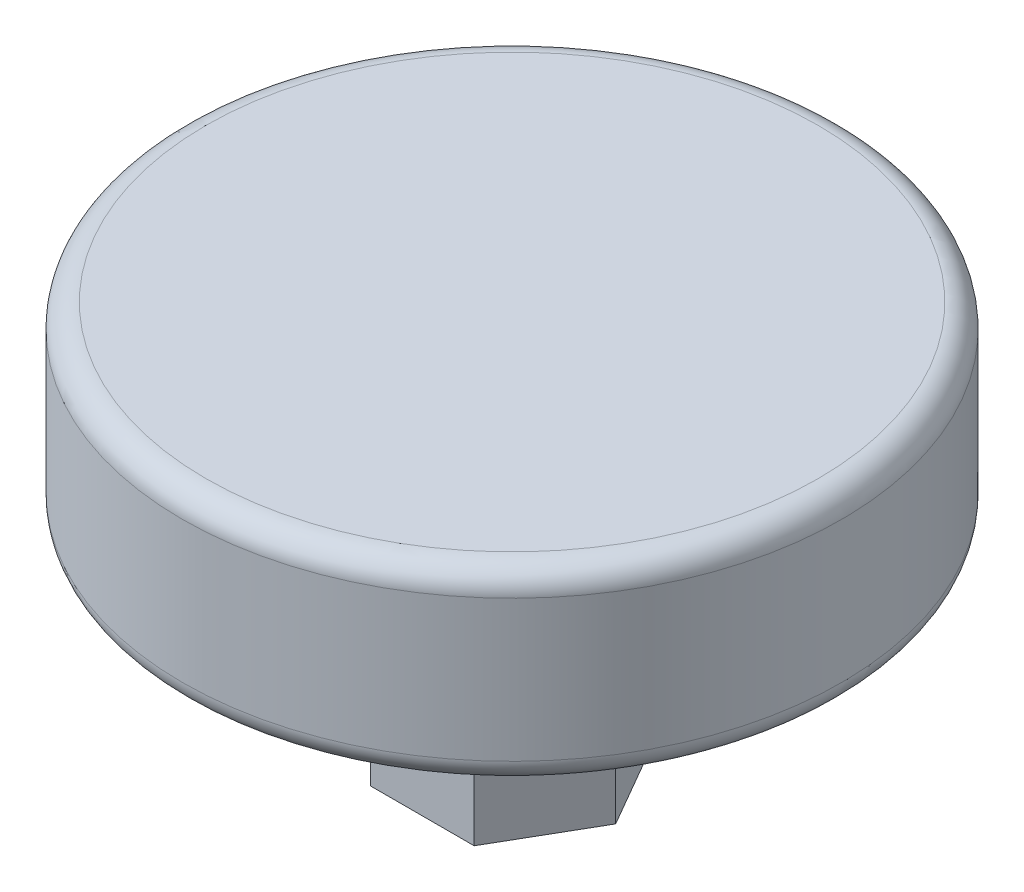
SolidWorks part; units mm, degrees
ref_plane "Front Plane" through (0, 0, 0) normal (0, 0, 1) x (1, 0, 0)
ref_plane "Top Plane" through (0, 0, 0) normal (0, 1, 0) x (1, 0, 0)
ref_plane "Right Plane" through (0, 0, 0) normal (1, 0, 0) x (0, 0, -1)
sketch "Sketch1" plane through (0, 0, 0) normal (0, 1, 0) x (1, 0, 0)
  line L1 (0.6582, 0) -> (0.3291, 0.57)
  line L2 (0.3291, 0.57) -> (-0.3291, 0.57)
  line L3 (-0.3291, 0.57) -> (-0.6582, 0)
  line L4 (-0.6582, 0) -> (-0.3291, -0.57)
  line L5 (-0.3291, -0.57) -> (0.3291, -0.57)
  line L6 (0.3291, -0.57) -> (0.6582, 0)
  circle A0 centre (0, 0) radius 0.57 construction
extrude "Boss-Extrude1" add sketch "Sketch1" along normal blind 1.75
sketch "Sketch2" plane through (0, 1.75, 0) normal (0, 1, 0) x (1, 0, 0)
  line L0 (0, 0) -> (0, -0.1986)
  line L1 (0.6582, 0) -> (0.3291, 0.57)
  line L2 (0.3291, 0.57) -> (-0.3291, 0.57)
  line L3 (-0.3291, 0.57) -> (-0.6582, 0)
  line L4 (-0.6582, 0) -> (-0.3291, -0.57)
  line L5 (-0.3291, -0.57) -> (0.3291, -0.57)
  line L6 (0.3291, -0.57) -> (0.6582, 0)
  line L7 (4.375, 0) -> (-2.1875, 3.7889) construction
  line L8 (-2.1875, 3.7889) -> (-2.1875, -3.7889) construction
  line L9 (-2.1875, -3.7889) -> (4.375, 0) construction
  line L10 (0, -0.1986) -> (0, 0.1978)
  line L11 (0, 0.1978) -> (4.375, 0)
  line L12 (4.375, 0) -> (0, -0.1986)
  circle A0 centre (0, 0) radius 0.57 construction
  circle A1 centre (0, 0) radius 4.375 construction
  line M2 (0.6582, 0) -> (0.3291, 0.57)
extrude "Boss-Extrude2" add sketch "Sketch2" along normal blind 0.5 contours L12 L11 L6 M2 | L12 L6 L11 L10 L0 M2 region at (0.2973, 1.75, 0.0004) region at (1.8638, 1.75, 0.0003)
sketch "Sketch3" plane through (0, 1.75, 0) normal (0, 1, 0) x (1, 0, 0)
  line L0 (0.6582, 0) -> (0.3291, 0.57)
  line L1 (-0.6582, 0) -> (-0.3291, -0.57)
  line L2 (-0.3291, -0.57) -> (0.3291, -0.57)
  line L3 (0.3291, -0.57) -> (0.6582, 0)
  line L4 (0.3291, 0.57) -> (-0.3291, 0.57)
  line L5 (-0.3291, 0.57) -> (-0.6582, 0)
  circle A0 centre (0, 0) radius 0.6582 construction
extrude "Boss-Extrude5" add sketch "Sketch3" along normal blind 3.5
sketch "Sketch4" plane through (0, 5.25, 0) normal (0, 1, 0) x (1, 0, 0)
  circle A0 centre (0, 0) radius 3.5
extrude "Boss-Extrude7" add sketch "Sketch4" along normal blind 2
sketch "Sketch11" plane through (0, 1.75, 0) normal (0, -1, 0) x (-1, 0, 0)
  circle A0 centre (0, 0) radius 4.5054
  circle A1 centre (0, 0) radius 3.5
extrude "Cut-Extrude3" cut sketch "Sketch11" against normal blind 2
sketch "Sketch12" plane through (0, 0, 0) normal (0, -1, 0) x (-1, 0, 0)
  circle A0 centre (0, 0) radius 3.5
extrude "Cut-Extrude4" cut sketch "Sketch12" against normal blind 3
fillet "Fillet3" radius 0.25 2 edges at (0, 7.25, 3.5) (0, 5.25, 3.5)
sketch "Sketch16" plane through (0, 3, 0) normal (0, -1, 0) x (-1, 0, 0)
  line L0 (1.1, 0) -> (-1.1, 0)
  line L1 (-1.1, 0) -> (-0.55, -0.9526)
  line L2 (-0.55, -0.9526) -> (0.55, -0.9526)
  line L3 (0.55, -0.9526) -> (1.1, 0)
  line L4 (1.1, 0) -> (0.55, 0.9526)
  line L5 (0.55, 0.9526) -> (-0.55, 0.9526)
  line L6 (-0.55, 0.9526) -> (-1.1, 0)
  circle A0 centre (0, 0) radius 0.9526 construction
  line M1 (-0.6582, 0) -> (-0.3291, -0.57)
  line M2 (-0.3291, -0.57) -> (0.3291, -0.57)
  line M3 (0.3291, -0.57) -> (0.6582, 0)
  line M4 (0.6582, 0) -> (0.3291, 0.57)
  line M5 (0.3291, 0.57) -> (-0.3291, 0.57)
  line M6 (-0.3291, 0.57) -> (-0.6582, 0)
  dimension "D1" = 2.2
extrude "Boss-Extrude8" add sketch "Sketch16" against normal blind 2.5 contours L2 L3 L0 L1 M3 M2 M1 | L5 L6 L0 L4 M6 M5 M4 | L0 M4 M5 M6 | L0 M3 M1 M2 region at (-0.8042, 3, 0.4643) region at (-0.8791, 3, -0.024) region at (0, 3, 0.2533) region at (0, 3, -0.2533)
chamfer "Chamfer1" distance 0.5 angle 30 6 edges at (0, 5.25, 0.9526) (-0.825, 5.25, 0.4763) (-0.825, 5.25, -0.4763) (0, 5.25, -0.9526) (0.825, 5.25, -0.4763) (0.825, 5.25, 0.4763) first distance on face at (0, 4.125, 0.9526) first distance on face at (-0.825, 4.125, 0.4763) first distance on face at (-0.825, 4.125, -0.4763) first distance on face at (0, 4.125, -0.9526) first distance on face at (0.825, 4.125, -0.4763) first distance on face at (0.825, 4.125, 0.4763)
